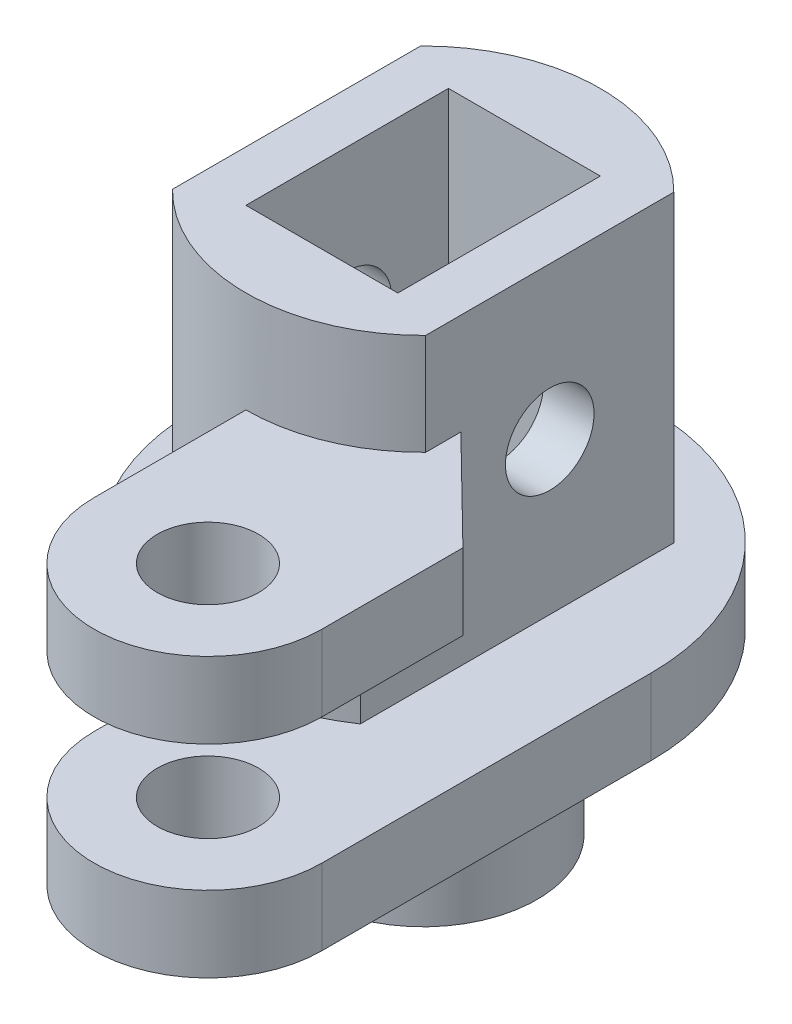
SolidWorks part; units mm, degrees
other "Markup1"
sketch "Sketch25" plane through (9, 15, 17.5) normal (0.6941, 0.3653, 0.6203) x (0.635, -0.7165, -0.2888)
ref_plane "Front Plane" through (0, 0, 0) normal (0, 0, 1) x (1, 0, 0)
ref_plane "Top Plane" through (0, 0, 0) normal (0, 1, 0) x (1, 0, 0)
ref_plane "Right Plane" through (0, 0, 0) normal (1, 0, 0) x (0, 0, -1)
sketch "Sketch1" plane through (0, 0, 0) normal (0, 1, 0) x (1, 0, 0)
  circle A0 centre (0, 0) radius 9
  dimension "D1" = 18
extrude "main body" add sketch "Sketch1" along normal blind 15
sketch "Sketch4" plane through (0, 0, 0) normal (0, -1, 0) x (1, 0, 0)
  circle A0 centre (0, 0) radius 6.5
  circle A1 centre (0, 0) radius 9 construction
  dimension "D1" = 13
extrude "Boss-Extrude3" add sketch "Sketch4" along normal blind 2 contours A0
sketch "Sketch5" plane through (0, -2, 0) normal (0, -1, 0) x (1, 0, 0)
  circle A0 centre (0, 0) radius 4.5
  circle A1 centre (0, 0) radius 6.5 construction
  dimension "D1" = 9
extrude "Boss-Extrude4" add sketch "Sketch5" along normal blind 5 contours A0
ref_plane "Plane1" through (0, 8, 0) normal (0, 1, 0) x (1, 0, 0)
sketch "Sketch9" plane through (0, 0, 0) normal (0, -1, 0) x (1, 0, 0)
  line L0 (0, 9) -> (0, 13)
  line L1 (9, 0) -> (9, 13)
  line L2 (0, 13) -> (9, 13) construction
  circle A0 centre (0, 0) radius 9 construction
  arc A2 (9, 0) -> (0, 9) centre (0, 0) ccw
  arc A3 (9, 13) -> (0, 13) centre (4.5, 13) ccw
  circle A4 centre (4.5, 13) radius 2
  dimension "D2" = 4.5
  dimension "D1" = 4
extrude "arm atttach" add sketch "Sketch9" against normal blind 3
ref_plane "Plane2" through (5, 0, 0) normal (1, 0, 0) x (0, 0, -1)
sketch "Sketch11" plane through (5, 0, 0) normal (1, 0, 0) x (0, 0, -1)
  line L0 (9, 0) -> (9, 15) construction
  line L1 (-9, 15) -> (9, 15)
  line L2 (-9, 15) -> (-9, 3)
  line L3 (-9, 3) -> (9, 3)
  line L4 (9, 15) -> (9, 3)
  dimension "D1" = 12
extrude "Cut-Extrude1" cut sketch "Sketch11" along normal blind 5
sketch "Sketch13" plane through (0, 8, 0) normal (0, 1, 0) x (1, 0, 0)
  line L0 (0, -13) -> (0, -9)
  line L1 (9, -13) -> (9, -7.4292)
  line L2 (9, -7.4292) -> (5, -3.5092)
  line L3 (5, -7.4833) -> (5, 7.4833) construction
  line L4 (5, -3.5092) -> (5, -7.4833)
  arc A0 (0, -13) -> (9, -13) centre (4.5, -13) ccw
  arc A1 (0, -9) -> (5, -7.4833) centre (0, 0) ccw
  circle A2 centre (4.5, -13) radius 2
extrude "arm attach" add sketch "Sketch13" along normal blind 3
ref_plane "Plane4" through (-5, 0, 0) normal (-1, 0, 0) x (0, 0, 1)
sketch "Sketch19" plane through (0, 15, 0) normal (0, 1, 0) x (1, 0, 0)
  line L0 (0, -7) -> (0, -9)
  line L1 (7.0839, -5.5514) -> (5.6441, -4.1405)
  line L2 (9, -7.4292) -> (5, -3.5092) construction
  arc A0 (5.6441, -4.1405) -> (0, -7) centre (0, 0) ccw
  arc A1 (7.0839, -5.5514) -> (0, -9) centre (0, 0) ccw
  dimension "D1" = 14
extrude "Cut-Extrude5" cut sketch "Sketch19" against normal up to surface (12 mm away) up to face at (4.8416, 3, 6.5616)
sketch "Sketch14" plane through (0, 15, 0) normal (0, 1, 0) x (1, 0, 0)
  line L1 (-3, 4) -> (3, 4)
  line L2 (-3, 4) -> (-3, -4)
  line L3 (-3, -4) -> (3, -4)
  line L4 (3, 4) -> (3, -4)
  line L5 (-3, 4) -> (3, -4) construction
  line L6 (-3, -4) -> (3, 4) construction
  point P0 (0, 0)
  dimension "D1" = 6
  dimension "D2" = 8
extrude "blade hole" cut sketch "Sketch14" against normal up to surface (12 mm away) up to face at (1.0369, 3, 5.4786)
sketch "Sketch21" plane through (-5, 0, 0) normal (-1, 0, 0) x (0, 0, 1)
  line L0 (-7, 9) -> (7, 9) construction
  line L1 (-7.5, 15) -> (7.5, 15)
  line L2 (-7.5, 15) -> (-7.5, 3)
  line L3 (-7.5, 3) -> (7.5, 3)
  line L4 (7.5, 15) -> (7.5, 3)
  line L5 (-7.5, 15) -> (7.5, 3) construction
  line L6 (-7.5, 3) -> (7.5, 15) construction
  line L7 (-7, 15) -> (-7, 3) construction
  line L8 (7, 3) -> (7, 15) construction
  point P0 (0, 9)
  dimension "D1" = 12
  dimension "D2" = 15
extrude "face cut" cut sketch "Sketch21" along normal blind 10
sketch "Sketch23" plane through (0, 15, 0) normal (0, 1, 0) x (1, 0, 0)
  circle A0 centre (0, 0) radius 7
  circle A1 centre (0, 0) radius 9
extrude "Cut-Extrude8" cut sketch "Sketch23" against normal up to surface (4 mm away) up to face at (4.6854, 11, 9.7154)
sketch "Sketch24" plane through (-5, 0, 0) normal (-1, 0, 0) x (0, 0, 1)
  line L0 (0, 15) -> (0, 3) construction
  line L1 (4.899, 15) -> (-4.899, 15) construction
  line L2 (9, 3) -> (-9, 3) construction
  circle A0 centre (0, 9) radius 1.75
  dimension "D1" = 3.5
extrude "screw hole" cut sketch "Sketch24" against normal mid plane 30
